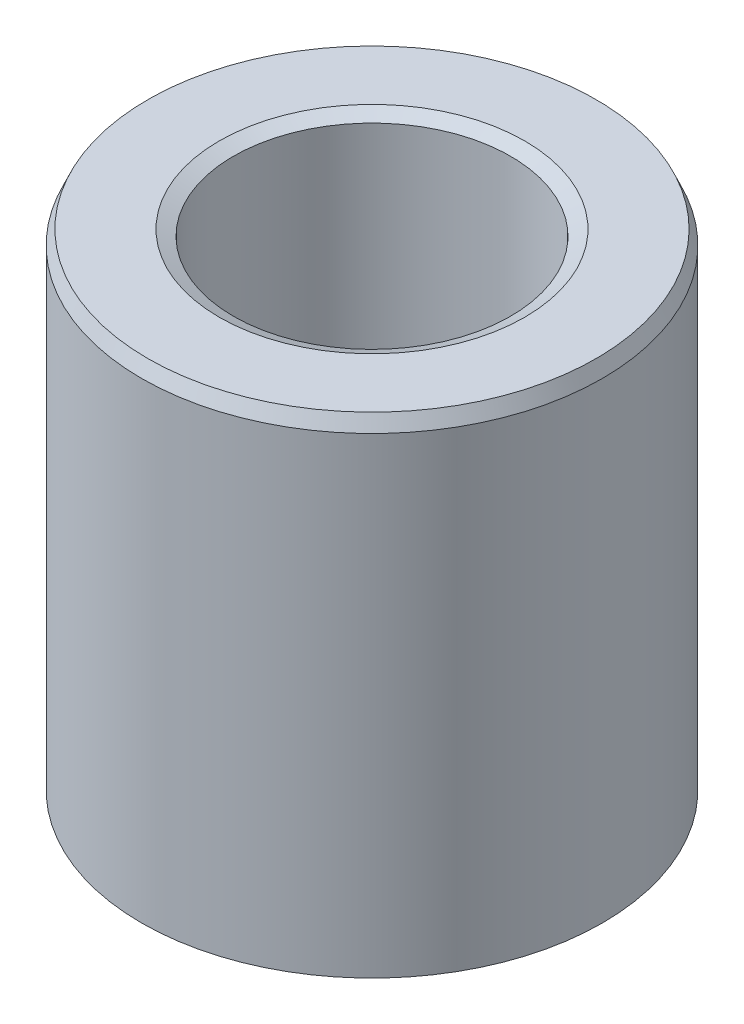
SolidWorks part; units mm, degrees
ref_plane "Front Plane" through (0, 0, 0) normal (0, 0, 1) x (1, 0, 0)
ref_plane "Top Plane" through (0, 0, 0) normal (0, 1, 0) x (1, 0, 0)
ref_plane "Right Plane" through (0, 0, 0) normal (1, 0, 0) x (0, 0, -1)
sketch "Sketch1" plane through (0, 0, 0) normal (0, 1, 0) x (1, 0, 0)
  circle A0 centre (0, 0) radius 32.5
  dimension "SLEEVE_OD" = 65
extrude "Boss-Extrude1" add sketch "Sketch1" along normal blind 69.3833
sketch "Sketch2" plane through (0, 0, 0) normal (0, 1, 0) x (1, 0, 0)
  circle A0 centre (0, 0) radius 19.5495
  dimension "BORE_D" = 39.0991
extrude "Cut-Extrude1" cut sketch "Sketch2" along normal through all
chamfer "Chamfer1" distance 1.993 angle 23.699 4 edges at (0, 69.3833, 19.5495) (0, 0, 19.5495) (0, 0, 32.5) (0, 69.3833, 32.5) first distance on face at (0, 69.3833, 19.5495) first distance on face at (0, 0, 19.5495) first distance on face at (0, 69.3833, 32.5)
